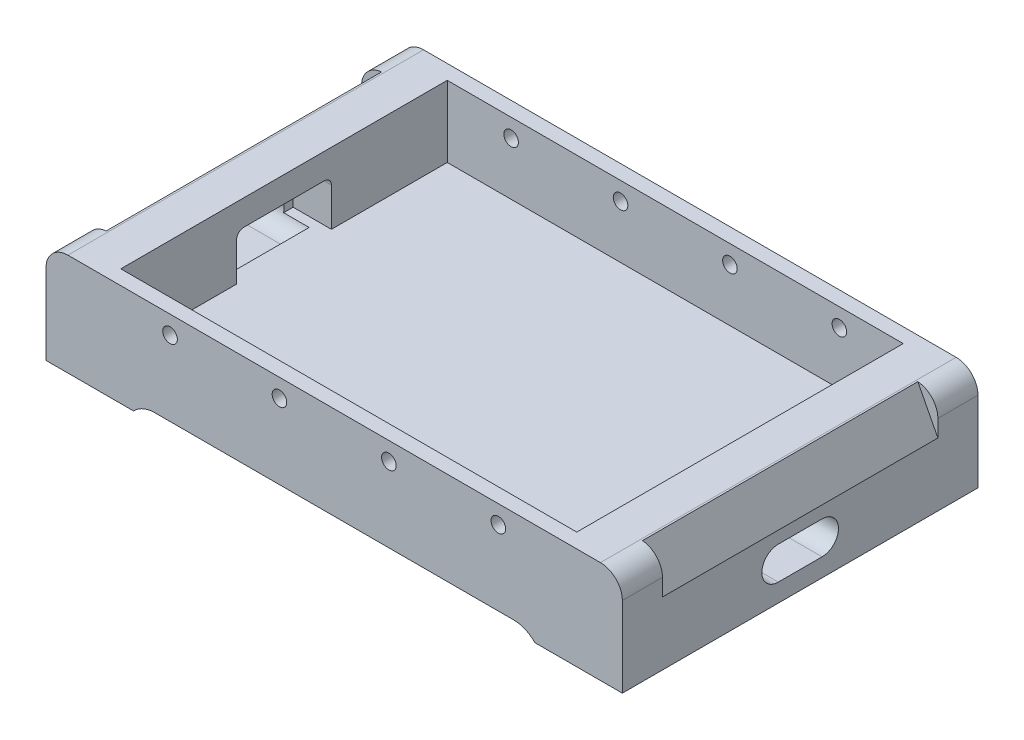
SolidWorks part; units mm, degrees
ref_plane "Front Plane" through (0, 0, 0) normal (0, 0, 1) x (1, 0, 0)
ref_plane "Top Plane" through (0, 0, 0) normal (0, 1, 0) x (1, 0, 0)
ref_plane "Right Plane" through (0, 0, 0) normal (1, 0, 0) x (0, 0, -1)
sketch "Sketch1" plane through (0, 0, 0) normal (0, 0, 1) x (1, 0, 0)
  line L1 (-250.825, -44.45) -> (250.825, -44.45)
  line L2 (-250.825, -44.45) -> (-250.825, 44.45)
  line L3 (-250.825, 44.45) -> (250.825, 44.45)
  line L4 (250.825, -44.45) -> (250.825, 44.45)
  line L5 (-250.825, -44.45) -> (250.825, 44.45) construction
  line L6 (-250.825, 44.45) -> (250.825, -44.45) construction
  point P0 (0, 0)
  dimension "D1" = 501.65
  dimension "D2" = 88.9
extrude "Boss-Extrude1" add sketch "Sketch1" along normal blind 309.5625
ref_plane "Plane1" through (0, 0, 154.7812) normal (0, 0, 1) x (1, 0, 0)
ref_plane "Plane2" through (0, 0, 0) normal (-1, 0, 0) x (0, 0, 1)
sketch "Sketch2" plane through (0, 0, 309.5625) normal (0, 0, 1) x (1, 0, 0)
  line L0 (-250.825, -44.45) -> (250.825, -44.45) construction
  line L1 (-174.625, -44.45) -> (174.625, -44.45)
  line L2 (-174.625, -44.45) -> (-174.625, -36.5125)
  line L3 (-174.625, -36.5125) -> (174.625, -36.5125)
  line L4 (174.625, -44.45) -> (174.625, -36.5125)
  line L5 (-174.625, -44.45) -> (174.625, -36.5125) construction
  line L6 (-174.625, -36.5125) -> (174.625, -44.45) construction
  line L7 (-250.825, 44.45) -> (-250.825, -44.45) construction
  line L8 (250.825, -44.45) -> (250.825, 44.45) construction
  point P0 (0, -40.4813)
  dimension "D1" = 7.9375
  dimension "D2" = 76.2
  dimension "D3" = 76.2
extrude "Cut-Extrude1" cut sketch "Sketch2" against normal through all
fillet "Fillet1" radius 25.4 2 edges at (174.625, -36.5125, 154.7812) (-174.625, -36.5125, 154.7812)
sketch "Sketch3" plane through (0, 0, 154.7812) normal (0, 0, 1) x (1, 0, 0)
  line L0 (-250.825, 44.45) -> (-233.3625, 44.45)
  line L1 (250.825, 44.45) -> (-250.825, 44.45) construction
  line L2 (-233.3625, 44.45) -> (-250.825, 10.5875)
  line L3 (-250.825, 44.45) -> (-250.825, -44.45) construction
  line L4 (-250.825, 10.5875) -> (-250.825, 44.45)
  dimension "D1" = 38.1
  dimension "D2" = 17.4625
extrude "Cut-Extrude2" cut sketch "Sketch3" along direction (0, 0, -1) on the side of the normal blind 119.8563 and the other way blind 119.8563
fillet "Fillet2" radius 19.05 2 edges at (-250.825, 44.45, 17.4625) (250.825, 44.45, 154.7812)
sketch "Sketch5" plane through (-250.825, 0, 0) normal (-1, 0, 0) x (0, 0, 1)
  line L0 (135.7312, -14.2875) -> (173.8312, -14.2875) construction
  line L1 (154.7812, -48.895) -> (154.7812, 48.895) construction
  line L2 (135.7312, 0) -> (173.8312, 0)
  line L3 (135.7312, -28.575) -> (173.8312, -28.575)
  line L4 (309.5625, -44.45) -> (0, -44.45) construction
  arc A0 (135.7312, 0) -> (135.7312, -28.575) centre (135.7312, -14.2875) ccw
  arc A1 (173.8312, -28.575) -> (173.8312, 0) centre (173.8312, -14.2875) ccw
  point P4 (154.7812, -14.2875)
  dimension "D3" = 38.1
  dimension "D1" = 15.875
  dimension "D2" = 28.575
extrude "Cut-Extrude4" cut sketch "Sketch5" against normal blind 41.275
mirror "Mirror4" about plane through (0, 0, 0) normal (-1, 0, 0) of "Cut-Extrude4", "Cut-Extrude2"
sketch "Sketch4" plane through (0, 44.45, 0) normal (0, 1, 0) x (1, 0, 0)
  line L0 (-48.895, -154.7812) -> (48.895, -154.7812) construction
  line L1 (-198.4375, -296.8625) -> (198.4375, -296.8625)
  line L2 (-198.4375, -296.8625) -> (-198.4375, -12.7)
  line L3 (-198.4375, -12.7) -> (198.4375, -12.7)
  line L4 (198.4375, -296.8625) -> (198.4375, -12.7)
  line L5 (-198.4375, -296.8625) -> (198.4375, -12.7) construction
  line L6 (-198.4375, -12.7) -> (198.4375, -296.8625) construction
  line L7 (0, 38.4175) -> (0, -38.4175) construction
  line L8 (231.775, 0) -> (-231.775, 0) construction
  line L9 (-250.825, -34.925) -> (-250.825, -274.6375) construction
  point P0 (0, -154.7812)
  dimension "D1" = 12.7
  dimension "D2" = 52.3875
extrude "Cut-Extrude3" cut sketch "Sketch4" against normal blind 61.9125
sketch "Sketch6" plane through (-198.4375, 0, 0) normal (-1, 0, 0) x (0, 0, 1)
  line L0 (154.7812, -48.895) -> (154.7812, 48.895) construction
  line L1 (113.5063, -17.4625) -> (196.0563, -17.4625)
  line L2 (113.5063, -17.4625) -> (113.5063, 22.225)
  line L3 (113.5063, 22.225) -> (196.0563, 22.225)
  line L4 (196.0563, -17.4625) -> (196.0563, 22.225)
  line L5 (113.5063, -17.4625) -> (196.0563, 22.225) construction
  line L6 (113.5063, 22.225) -> (196.0563, -17.4625) construction
  line L7 (296.8625, -17.4625) -> (12.7, -17.4625) construction
  line L8 (296.8625, 44.45) -> (12.7, 44.45) construction
  point P0 (154.7812, 2.3812)
  dimension "D1" = 22.225
  dimension "D2" = 82.55
extrude "Cut-Extrude5" cut sketch "Sketch6" along normal up to vertex (33.3375 mm away) up to point (-231.775, 44.45, 0)
fillet "Fillet3" radius 6.35 2 edges at (-215.1063, 22.225, 196.0563) (-215.1063, 22.225, 113.5063)
sketch "Sketch7" plane through (0, 0, 309.5625) normal (0, 0, 1) x (1, 0, 0)
  line L0 (0, 44.45) -> (0, -36.5125) construction
  line L1 (231.775, 44.45) -> (-231.775, 44.45) construction
  line L2 (156.1799, -36.5125) -> (-156.1799, -36.5125) construction
  line L3 (-250.825, 28.575) -> (250.825, 28.575) construction
  line L4 (-250.825, 25.4) -> (-250.825, -44.45) construction
  line L5 (250.825, -44.45) -> (250.825, 25.4) construction
  line L6 (-250.825, -44.45) -> (-174.625, -44.45) construction
  circle A0 centre (-47.625, 28.575) radius 6.35
  circle A1 centre (-142.875, 28.575) radius 6.35
  point P16 (0, 3.9687)
  dimension "D2" = 12.7
  dimension "D1" = 73.025
  dimension "D3" = 47.625
  dimension "D4" = 95.25
extrude "Cut-Extrude6" cut sketch "Sketch7" against normal through all
mirror "Mirror5" about plane through (0, 0, 0) normal (-1, 0, 0) of "Cut-Extrude6", "Cut-Extrude5", "Fillet3"
